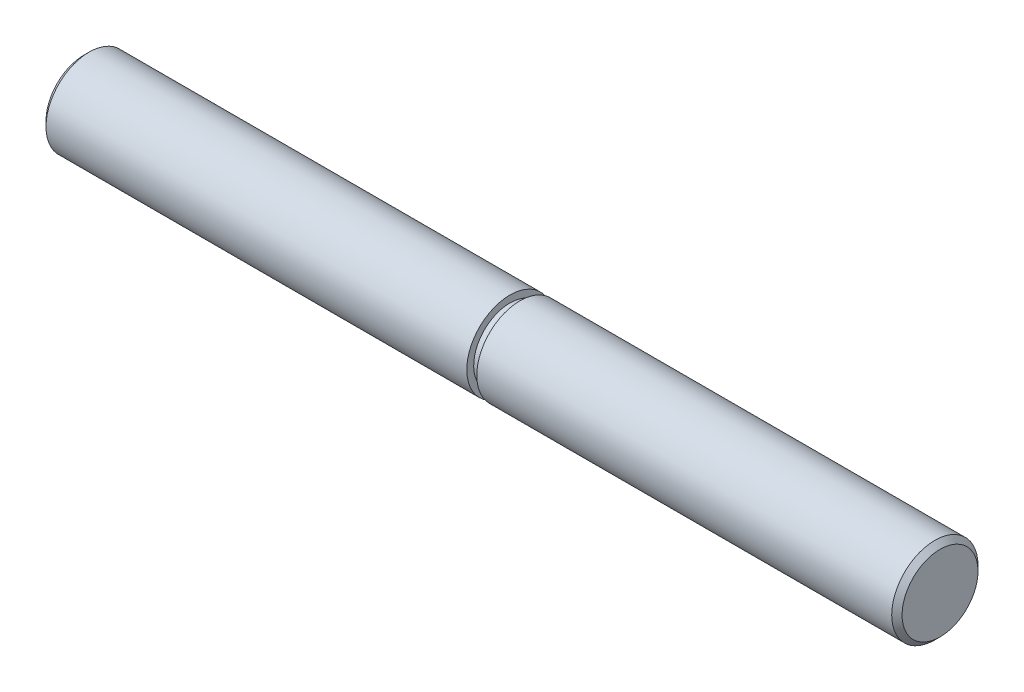
SolidWorks part; units mm, degrees
material "AISI 1015 Steel, Cold Drawn (SS)"
ref_plane "Front" through (0, 0, 0) normal (0, 0, 1) x (1, 0, 0)
ref_plane "Top" through (0, 0, 0) normal (0, 1, 0) x (1, 0, 0)
ref_plane "Right" through (0, 0, 0) normal (1, 0, 0) x (0, 0, -1)
ref_axis "side-side" through (80.9, 0, 0) along (-1, 0, 0)
ref_axis "up-down" through (0, 50, 0) along (0, -1, 0)
ref_axis "front-back" through (0, 0, -80.9) along (0, 0, 1)
sketch "Sketch2" plane through (0, 0, 0) normal (0, 0, 1) x (1, 0, 0)
  line L0 (-31.496, 0) -> (-38.3289, 0) construction
  line L1 (-31.496, 0) -> (31.496, 0)
  line L2 (-31.496, 0) -> (-31.496, 3.175)
  line L3 (-31.496, 3.175) -> (-0.1524, 3.175)
  line L4 (31.496, 0) -> (31.496, 3.175)
  line L5 (0.5842, 3.175) -> (31.496, 3.175)
  line L7 (-0.1524, 3.175) -> (-0.1524, 2.667)
  line L8 (-0.1524, 2.667) -> (0.5842, 2.667)
  line L9 (0.5842, 3.175) -> (0.5842, 2.667)
  dimension "D1" = 6.35
  dimension "D2" = 62.992
  dimension "D3" = 5.334
  dimension "D4" = 0.7366
  dimension "D5" = 31.3436
revolve "Revolve1" add sketch "Sketch2" angle 360 about L0
chamfer "Chamfer1" distance 0.381 angle 45 2 edges at (31.496, 3.175, 0) (-31.496, 3.175, 0)
